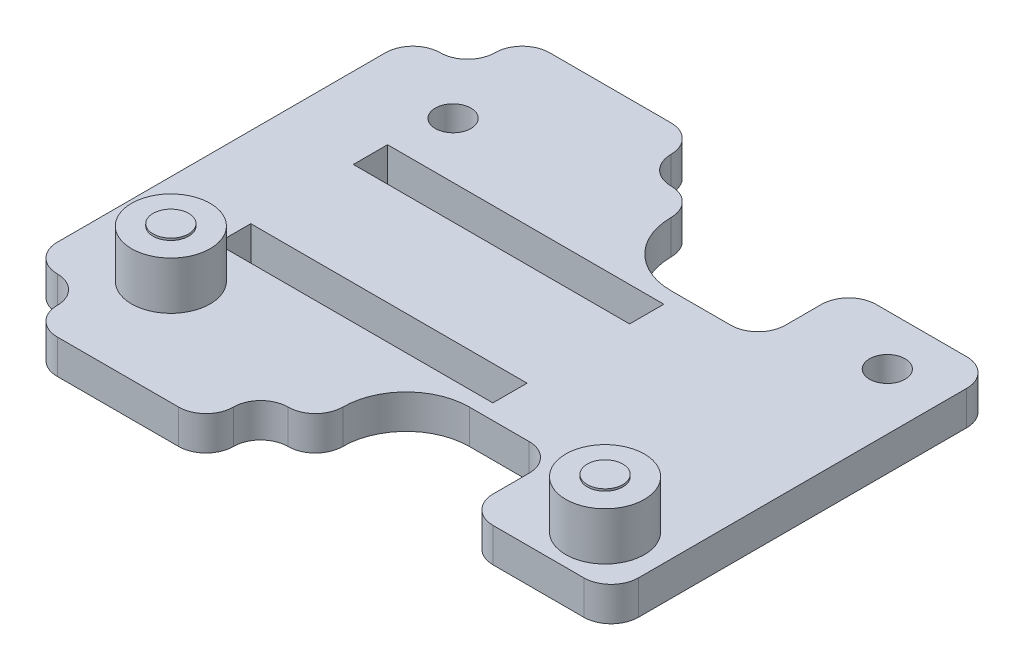
SolidWorks part; units mm, degrees
other "下垫片"
ref_plane "前视基准面" through (0, 0, 0) normal (0, 0, 1) x (1, 0, 0)
ref_plane "上视基准面" through (0, 0, 0) normal (0, 1, 0) x (1, 0, 0)
ref_plane "右视基准面" through (0, 0, 0) normal (1, 0, 0) x (0, 0, -1)
other "Configuration Table"
sketch "草图1" plane through (0, 0, 0) normal (0, 1, 0) x (1, 0, 0)
  line L0 (-89.3251, 0) -> (102.0425, 0) construction
  line L1 (0, 56.7239) -> (0, -62.578) construction
  line L2 (-33.2, -7.5) -> (7.2, -7.5)
  line L3 (-33.2, 12.5) -> (7.2, 12.5)
  line L4 (-33.2, 12.5) -> (-33.2, 7.5)
  line L5 (-33.2, 7.5) -> (7.2, 7.5)
  line L6 (7.2, 12.5) -> (7.2, 7.5)
  line L7 (-33.2, 12.5) -> (7.2, 7.5) construction
  line L8 (-33.2, 7.5) -> (7.2, 12.5) construction
  line L9 (7.2, -12.5) -> (7.2, -7.5)
  line L10 (-33.2, -12.5) -> (7.2, -12.5)
  line L11 (-33.2, -12.5) -> (-33.2, -7.5)
  line L14 (-3.25, -26.5375) -> (-3.25, -14.7375)
  line L15 (-3.25, -14.7375) -> (18.75, -14.7375)
  line L16 (18.75, -26.5375) -> (18.75, -14.7375)
  line L17 (-3.25, -26.5375) -> (18.75, -14.7375) construction
  line L18 (-3.25, -14.7375) -> (18.75, -26.5375) construction
  line L19 (-3.25, 14.7375) -> (18.75, 14.7375)
  line L20 (18.75, 26.5375) -> (18.75, 14.7375)
  line L22 (-3.25, 26.5375) -> (-3.25, 14.7375)
  line L23 (-3.25, 29.8695) -> (18.75, 29.8695)
  line L25 (-3.25, -26.5375) -> (-3.25, -29.8695)
  line L26 (-3.25, -29.8695) -> (18.75, -29.8695)
  line L27 (18.75, -26.5375) -> (18.75, -29.8695)
  line L28 (18.75, 26.5375) -> (18.75, 29.8695)
  line L30 (-3.25, 26.5375) -> (-3.25, 29.8695)
  circle A0 centre (-31.75, 20.6375) radius 2.6
  circle A4 centre (31.75, 20.6375) radius 2.6
  circle A5 centre (31.75, -20.6375) radius 2.6
  circle A6 centre (-31.75, -20.6375) radius 2.6
  point P13 (-13, 10)
  point P22 (7.75, -20.6375)
  point P35 (-13, 10)
  dimension "D5" = 5.2
  dimension "D11" = 5.2
  dimension "D1" = 40.4
  dimension "D2" = 31.75
  dimension "D3" = 5
  dimension "D4" = 20.6375
  dimension "D6" = 11.8
  dimension "D7" = 22
  dimension "D8" = 11.8
  dimension "D9" = 0
  dimension "D10" = 13
  dimension "D12" = 5
  dimension "D13" = 40.4
  dimension "D14" = 13
  dimension "D15" = 10
  dimension "D16" = 2.2375
sketch "草图3" plane through (0, 0, 0) normal (0, 1, 0) x (1, 0, 0)
  line L0 (-55, 0) -> (55, 0) construction
  line L1 (-11.25, -28) -> (40, -28)
  line L3 (-11.25, 28) -> (40, 28)
  line L4 (40, -28) -> (40, 28)
  line L5 (-40, -28) -> (40, 28) construction
  line L6 (-40, 28) -> (40, -28) construction
  line L10 (-45, 28) -> (-45, -28)
  line L15 (-11.25, 28) -> (-11.25, 36)
  line L16 (-37, 36) -> (-11.25, 36)
  line L18 (-45, 28) -> (-37, 28)
  line L19 (-37, 28) -> (-37, 36)
  line L20 (-11.25, -28) -> (-11.25, -36)
  line L21 (-37, -36) -> (-11.25, -36)
  line L22 (-37, -28) -> (-37, -36)
  line L23 (-45, -28) -> (-37, -28)
  point P0 (0, 0)
  dimension "D1" = 56
  dimension "D2" = 80
  dimension "D3" = 5
  dimension "D4" = 8
  dimension "D5" = 25.75
  dimension "D6" = 8
extrude "凸台-拉伸1" add sketch "草图3" along normal blind 5
extrude "切除-拉伸1" cut sketch "草图1" along normal up to surface (5 mm away) up to face at (-16.9167, 5, 0)
sketch "草图5" plane through (0, 5, 0) normal (0, 1, 0) x (1, 0, 0)
  circle A0 centre (31.75, -20.6375) radius 5.75
  dimension "D1" = 11.5
extrude "凸台-拉伸2" add sketch "草图5" along normal blind 7
sketch "草图6" plane through (0, 12, 0) normal (0, 1, 0) x (1, 0, 0)
  circle A0 centre (31.75, -20.6375) radius 2.6
  dimension "D1" = 5.2
extrude "凸台-拉伸3" add sketch "草图6" along normal blind 0.3
fillet "圆角2" radius 4 18 edges at (-3.25, 2.5, -28) (18.75, 2.5, -28) (40, 2.5, -28) (40, 2.5, 28) (18.75, 2.5, 28) (-3.25, 2.5, 28) (18.75, 2.5, -14.7375) (18.75, 2.5, 14.7375) (-11.25, 2.5, 28) (-11.25, 2.5, 36) (-11.25, 2.5, -36) (-11.25, 2.5, -28) (-37, 2.5, 36) (-37, 2.5, 28) (-45, 2.5, 28) (-45, 2.5, -28) (-37, 2.5, -28) (-37, 2.5, -36)
mirror "镜向1" about plane through (0, 0, 0) normal (1, 0, 0) of "凸台-拉伸3", "凸台-拉伸2"
fillet "圆角3" radius 9.2625 2 edges at (-3.25, 2.5, -14.7375) (-3.25, 2.5, 14.7375)
